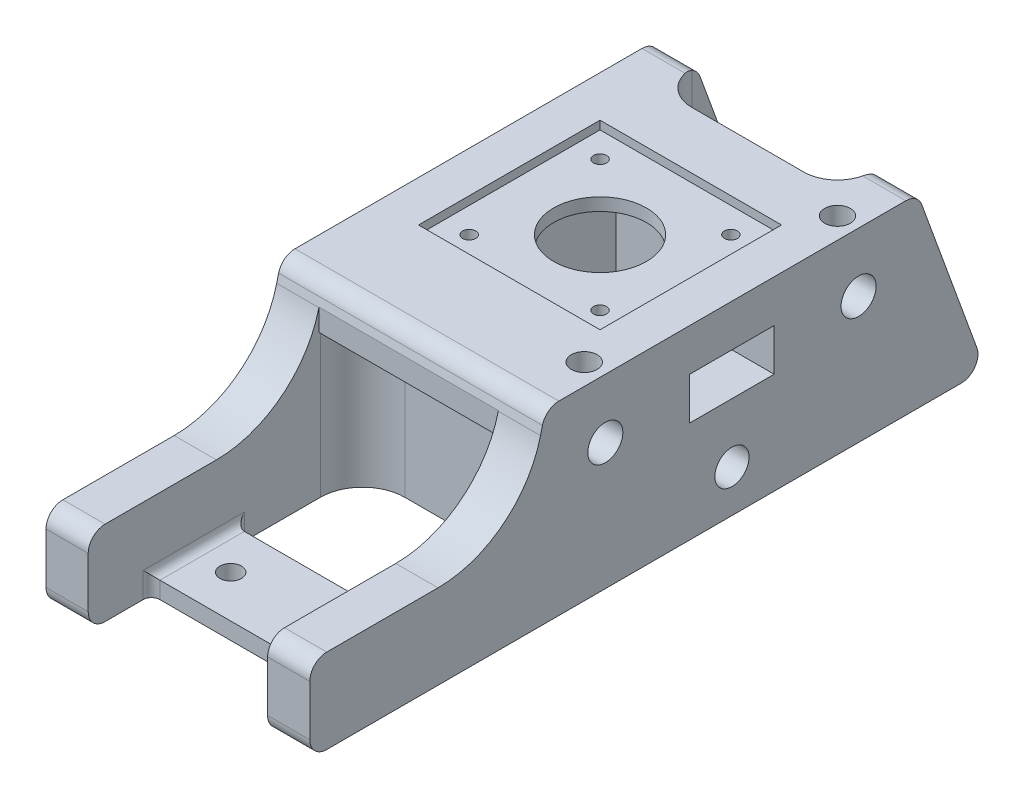
SolidWorks part; units mm, degrees
note: '?' marks a value the reader was unsure of.
material "PLA (20%–30% infill + wall)"
ref_plane "Front Plane" through (0, 0, 0) normal (0, 0, 1) x (1, 0, 0)
ref_plane "Top Plane" through (0, 0, 0) normal (0, 1, 0) x (1, 0, 0)
ref_plane "Right Plane" through (0, 0, 0) normal (1, 0, 0) x (0, 0, -1)
sketch "Sketch3" plane through (0, 0, 0) normal (1, 0, 0) x (0, 0, -1)
  line L0 (-29.0504, 0) -> (36.0735, 0) construction
  line L1 (36.0735, 0) -> (0, 0) construction
  line L2 (0, 0) -> (0, 40.7024) construction
  line L3 (60, 0) -> (-100, 0)
  line L4 (-100, 0) -> (-100, 20)
  line L6 (-44.1548, 44) -> (43.9853, 44)
  line L7 (43.9853, 44) -> (60, 0)
  line L8 (-100, 20) -> (-50, 20)
  line L9 (-44.1548, 44) -> (-50, 20)
  circle A0 centre (-30, 30) radius 4.15
  circle A1 centre (30, 30) radius 4.15
  dimension "D1" = 8.3
  dimension "D2" = 60
  dimension "D3" = 30
  dimension "D7" = 70
  dimension "D8" = 14
  dimension "D4" = 30
  dimension "D5" = 70
  dimension "D6" = 20
  dimension "D9" = 50
extrude "Boss-Extrude2" add sketch "Sketch3" along normal blind 10
fillet "Fillet1" radius 4 3 edges at (5, 0, 100) (5, 44, -43.9853) (5, 0, -60)
sketch "Sketch4" plane through (0, 0, 0) normal (-1, 0, 0) x (0, 0, 1)
  line L0 (-47.625, 34) -> (67.8352, 34)
  line L1 (45.3226, 43.675) -> (45.3226, 34)
  line L2 (-34.995, 34) -> (-34.995, 44)
  line L5 (100, 20) -> (50, 20)
  line L6 (44.1548, 44) -> (-41.1845, 44)
  line L7 (-44.9433, 41.3681) -> (-58.0462, 5.3681)
  line L8 (-54.2874, 0) -> (96, 0)
  line L9 (100, 4) -> (100, 20)
  line L11 (44.1548, 44) -> (-41.1845, 44)
  line L12 (-44.9433, 41.3681) -> (-58.0462, 5.3681)
  line L13 (-54.2874, 0) -> (96, 0)
  line L14 (100, 4) -> (100, 20)
  line L18 (100, 20) -> (50, 20)
  line L19 (50, 20) -> (44.1548, 44)
  line L20 (50, 20) -> (44.1548, 44)
  arc A6 (-41.1845, 44) -> (-44.9433, 41.3681) centre (-41.1845, 40) ccw
  arc A7 (-58.0462, 5.3681) -> (-54.2874, 0) centre (-54.2874, 4) ccw
  arc A8 (96, 0) -> (100, 4) centre (96, 4) ccw
  arc A11 (-41.1845, 44) -> (-44.9433, 41.3681) centre (-41.1845, 40) ccw
  arc A12 (-58.0462, 5.3681) -> (-54.2874, 0) centre (-54.2874, 4) ccw
  arc A13 (96, 0) -> (100, 4) centre (96, 4) ccw
  point P12 (1.4851, 44)
  dimension "D2" = 10
  dimension "D3" = 12.63
  dimension "D1" = 0
extrude "Boss-Extrude3" add sketch "Sketch4" along normal blind 42.5
ref_plane "Plane1" through (-21.25, 0, 0) normal (-1, 0, 0) x (0, 0, 1)
mirror "Mirror1" about plane through (-21.25, 0, 0) normal (-1, 0, 0) of "Fillet1", "Boss-Extrude2"
sketch "Sketch5" plane through (10, 0, 0) normal (1, 0, 0) x (0, 0, -1)
  line L0 (-25.85, 30) -> (25.85, 30) construction
  line L2 (-10, 34) -> (10, 34)
  line L3 (-10, 34) -> (-10, 24)
  line L4 (-10, 24) -> (10, 24)
  line L5 (10, 34) -> (10, 24)
  line L6 (-10, 34) -> (10, 24) construction
  line L7 (-10, 24) -> (10, 34) construction
  circle A0 centre (-30, 30) radius 4.15 construction
  circle A1 centre (30, 30) radius 4.15 construction
  point P7 (0, 30)
  dimension "D1" = 10
  dimension "D2" = 20
  dimension "D3" = 4
extrude "Cut-Extrude1" cut sketch "Sketch5" against normal up to surface (10 mm away) up to face at (0, 25.2767, 10.4506)
ref_axis "Axis1" through (10, 34, 0) along (-1, 0, 0)?
sketch "Sketch6" plane through (0, 34, 0) normal (0, -1, 0) x (1, 0, 0)
  line L0 (-21.25, 21.5628) -> (-21.25, -21.5628) construction
  line L1 (10, 0) -> (-44.2154, 0) construction
  circle A0 centre (-21.25, 0) radius 11
  dimension "D1" = 22
extrude "Cut-Extrude2" cut sketch "Sketch6" against normal up to surface (10 mm away) up to face at (-21.25, 44, -18.3023)
sketch "Sketch7" plane through (0, 44, 0) normal (0, 1, 0) x (1, 0, 0)
  line L1 (-42.75, -21.5) -> (0.25, -21.5)
  line L2 (-42.75, -21.5) -> (-42.75, 21.5)
  line L3 (-42.75, 21.5) -> (0.25, 21.5)
  line L4 (0.25, -21.5) -> (0.25, 21.5)
  line L5 (-42.75, -21.5) -> (0.25, 21.5) construction
  line L6 (-42.75, 21.5) -> (0.25, -21.5) construction
  point P0 (-21.25, 0)
  dimension "D1" = 43
extrude "Cut-Extrude3" cut sketch "Sketch7" against normal blind 2
sketch "Sketch8" plane through (0, 42, 0) normal (0, 1, 0) x (1, 0, 0)
  line L0 (-42.75, -21.5) -> (0.25, 21.5) construction
  line L1 (0.25, 21.5) -> (-42.75, 21.5) construction
  line L2 (-42.75, 21.5) -> (0.25, -21.5) construction
  line L3 (-21.25, 21.5628) -> (-21.25, -21.5628) construction
  line L4 (-21.25, 0) -> (0, 0) construction
  circle A0 centre (-36.75, 15.5) radius 1.55
  circle A1 centre (-5.75, 15.5) radius 1.55
  circle A2 centre (-5.75, -15.5) radius 1.55
  circle A3 centre (-36.75, -15.5) radius 1.55
  dimension "D1" = 3.1
  dimension "D2" = 31
extrude "Cut-Extrude4" cut sketch "Sketch8" against normal blind 5
sketch "Sketch9" plane through (0, 0, 0) normal (-1, 0, 0) x (0, 0, 1)
  line L0 (96, 0) -> (-54.2874, 0) construction
  line L1 (25, 34.15) -> (35, 34.15)
  line L2 (25, 34.15) -> (25, 0)
  line L3 (25, 0) -> (35, 0)
  line L4 (35, 34.15) -> (35, 0)
  line L5 (30, 30) -> (30, 0) construction
  circle A0 centre (30, 30) radius 4.15 construction
  point P11 (30, 34.15)
  dimension "D1" = 10
extrude "Boss-Extrude4" add sketch "Sketch9" along normal up to surface (42.5 mm away) up to face at (-42.5, 25.2767, 10.4506)
ref_plane "Plane2" through (0, 0, 0) normal (0, 0, -1) x (-1, 0, 0)
mirror "Mirror2" about plane through (0, 0, 0) normal (0, 0, -1) of "Boss-Extrude4"
fillet "Fillet2" radius 10 2 edges at (0, 17, 35) (-42.5, 17, 35)
fillet "Fillet3" radius 8 2 edges at (0, 17.075, -35) (-42.5, 17.075, -35)
sketch "Sketch10" plane through (-52.5, 0, 0) normal (-1, 0, 0) x (0, 0, 1)
  circle A0 centre (30, 30) radius 4.15 construction
  circle A1 centre (-30, 30) radius 4.15 construction
  circle A2 centre (30, 30) radius 4.15
  circle A3 centre (-30, 30) radius 4.15
extrude "Boss-Extrude5" add sketch "Sketch10" against normal up to surface (10 mm away) up to face at (-42.5, 30, -25.85)
sketch "Sketch11" plane through (10, 0, 0) normal (1, 0, 0) x (0, 0, -1)
  line L0 (0, 24) -> (0, 0) construction
  line L1 (-10, 24) -> (10, 24) construction
  line L2 (-96, 0) -> (54.2874, 0) construction
  circle A0 centre (0, 10) radius 4.05
  dimension "D1" = 8.1
  dimension "D2" = 10
extrude "Cut-Extrude5" cut sketch "Sketch11" against normal blind 77
fillet "Fillet4" radius 25 2 edges at (5, 20, 50) (-47.5, 20, 50)
fillet "Fillet5" radius 4 2 edges at (5, 20, 100) (-47.5, 20, 100)
fillet "Fillet6" radius 4 1 edges at (-21.25, 44, 44.1548)
sketch "Sketch12" plane through (10, 0, 0) normal (1, 0, 0) x (0, 0, -1)
  line L0 (-30, 34.15) -> (-30, 44) construction
  line L1 (41.1845, 44) -> (-41.012, 44) construction
  line L2 (30, 34.15) -> (30, 44) construction
  circle A0 centre (-30, 30) radius 4.15 construction
  circle A1 centre (-30, 30) radius 4.15 construction
  circle A2 centre (30, 30) radius 4.15 construction
  circle A3 centre (30, 30) radius 4.15 construction
sketch "Sketch13" plane through (0, 44, 0) normal (0, 1, 0) x (1, 0, 0)
  line L0 (10, -30) -> (-52.5, -30) construction
  line L1 (-52.5, 41.1845) -> (-52.5, -41.012) construction
  line L2 (10, 30) -> (-52.5, 30) construction
  line L3 (10, 41.1845) -> (10, -41.012) construction
  line L4 (5.5, 0) -> (-5.5, 0) construction
  circle A0 centre (5, -30) radius 3.05
  circle A1 centre (5, 30) radius 3.05
  point P0 (10, 30)
  point P2 (10, -30)
  dimension "D1" = 6.1
  dimension "D2" = 5
extrude "Cut-Extrude6" cut sketch "Sketch13" against normal blind 12
sketch "Sketch14" plane through (-42.5, 0, 0) normal (1, 0, 0) x (0, 0, -1)
  line L0 (-96, 0) -> (-45, 0) construction
  line L1 (-85, 0) -> (-65, 0)
  line L2 (-85, 0) -> (-85, 4)
  line L3 (-85, 4) -> (-65, 4)
  line L4 (-65, 0) -> (-65, 4)
  line L5 (-100, 16) -> (-100, 4) construction
  dimension "D1" = 20
  dimension "D2" = 4
  dimension "D3" = 15
extrude "Boss-Extrude6" add sketch "Sketch14" along normal up to surface (42.5 mm away) up to face at (0, 20.2089, 68.5996)
fillet "Fillet7" radius 2 4 edges at (-42.5, 2, 65) (0, 2, 65) (0, 2, 85) (-42.5, 2, 85)
sketch "Sketch16" plane through (0, 34, 0) normal (0, -1, 0) x (-1, 0, 0)
  line L1 (41.25, -20) -> (1.25, -20)
  line L2 (41.25, -20) -> (41.25, 20)
  line L3 (41.25, 20) -> (1.25, 20)
  line L4 (1.25, -20) -> (1.25, 20)
  line L5 (41.25, -20) -> (1.25, 20) construction
  line L6 (41.25, 20) -> (1.25, -20) construction
  point P0 (21.25, 0)
  dimension "D1" = 40
  dimension "D2" = 40
extrude "Cut-Extrude8" cut sketch "Sketch16" against normal blind 5
fillet "Fillet9" radius 2 2 edges at (0, 4, 75) (-42.5, 4, 75)
sketch "Sketch17" plane through (0, 0, 0) normal (0, -1, 0) x (-1, 0, 0)
  line L0 (42.5, 48.6437) -> (0, 48.6437)
  line L1 (42.5, 43) -> (42.5, 54.2874) construction
  line L2 (0, 43) -> (0, 54.2874) construction
  line L3 (34.5, 35) -> (8, 35) construction
  line L4 (0, 43) -> (0, 48.6437)
  line L5 (42.5, 43) -> (42.5, 48.6437)
  line L6 (34.5, 35) -> (8, 35)
  arc A1 (34.5, 35) -> (42.5, 43) centre (34.5, 43) ccw construction
  arc A2 (0, 43) -> (8, 35) centre (8, 43) ccw
  arc A3 (34.5, 35) -> (42.5, 43) centre (34.5, 43) ccw
extrude "Boss-Extrude7" add sketch "Sketch17" against normal blind 4
fillet "Fillet10" radius 8 2 edges at (0, 39.075, -34.995) (-42.5, 39.075, -34.995)
sketch "Sketch18" plane through (0, 4, 0) normal (0, 1, 0) x (1, 0, 0)
  line L0 (-21.25, 48.6437) -> (-21.25, -84.5292) construction
  line L1 (-42.5, 48.6437) -> (0, 48.6437) construction
  line L2 (-21.25, 21.5628) -> (-21.25, -21.5628) construction
  line L3 (-40.5, -75) -> (-2, -75) construction
  line L4 (-40.5, -65) -> (-40.5, -85) construction
  line L5 (-2, -85) -> (-2, -65) construction
  circle A0 centre (-33.75, 42.1437) radius 2.55
  circle A1 centre (-33.75, -75) radius 2.55
  circle A2 centre (-8.75, -75) radius 2.55
  circle A3 centre (-8.75, 42.1437) radius 2.55
  dimension "D1" = 5.1
  dimension "D2" = 5.1
  dimension "D3" = 25
  dimension "D4" = 25
  dimension "D5" = 6.5
extrude "Cut-Extrude9" cut sketch "Sketch18" against normal through all
fillet "Fillet11" radius 2 5 edges at (0, 4, -45.8219) (-2.3431, 4, -37.3431) (-42.5, 4, -45.8219) (-40.1569, 4, -37.3431) (-21.25, 4, -35)
